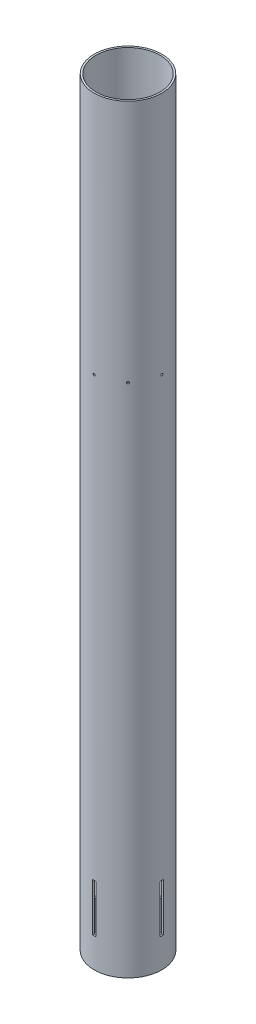
SolidWorks part; units mm, degrees
material "Hexcel AS4C (3000 Filaments)"
ref_plane "Front Plane" through (0, 0, 0) normal (0, 0, 1) x (1, 0, 0)
ref_plane "Top Plane" through (0, 0, 0) normal (0, 1, 0) x (1, 0, 0)
ref_plane "Right Plane" through (0, 0, 0) normal (1, 0, 0) x (0, 0, -1)
sketch "Sketch1" plane through (0, 0, 0) normal (0, 1, 0) x (1, 0, 0)
  circle A0 centre (0, 0) radius 50.8
  dimension "D1" = 101.6
extrude "Body Tube Extrusion" add sketch "Sketch1" along normal blind 1206.5 thin thin type one direction wall 2.921
ref_plane "Plane1" through (0, 0, 53.721) normal (0, 0, 1) x (1, 0, 0)
sketch "Sketch2" plane through (0, 0, 53.721) normal (0, 0, 1) x (1, 0, 0)
  line L0 (0, 1206.5) -> (0, 0) construction
  line L1 (50.8, 1206.5) -> (-50.8, 1206.5) construction
  line L2 (-53.721, 0) -> (53.721, 0) construction
  circle A0 centre (0, 819.15) radius 1.6383
  dimension "D1" = 3.2766
  dimension "D2" = 819.15
extrude "Engine Block Hole" cut sketch "Sketch2" against normal up to next
pattern_circular "CirPattern1" count 8 over 360 about axis through (0, 1206.5, 0) along (0, -1, 0) of "Engine Block Hole"
sketch "Sketch3" plane through (0, 0, 53.721) normal (0, 0, 1) x (1, 0, 0)
  line L0 (0, 0) -> (0, 46.99) construction
  line L1 (-50.8, 0) -> (50.8, 0) construction
  line L2 (0, 1206.5) -> (0, 0) construction
  line L4 (-2.667, 123.19) -> (2.667, 123.19)
  line L5 (-2.667, 123.19) -> (-2.667, 46.99)
  line L6 (-2.667, 46.99) -> (2.667, 46.99)
  line L7 (2.667, 123.19) -> (2.667, 46.99)
  point P10 (0, 46.99)
  dimension "D1" = 76.2
  dimension "D2" = 5.334
  dimension "D3" = 46.99
extrude "Fin Tab Slots" cut sketch "Sketch3" against normal up to next
pattern_circular "CirPattern2" count 4 over 360 about axis through (0, 1206.5, 0) along (0, -1, 0) of "Fin Tab Slots" reverse direction yes
